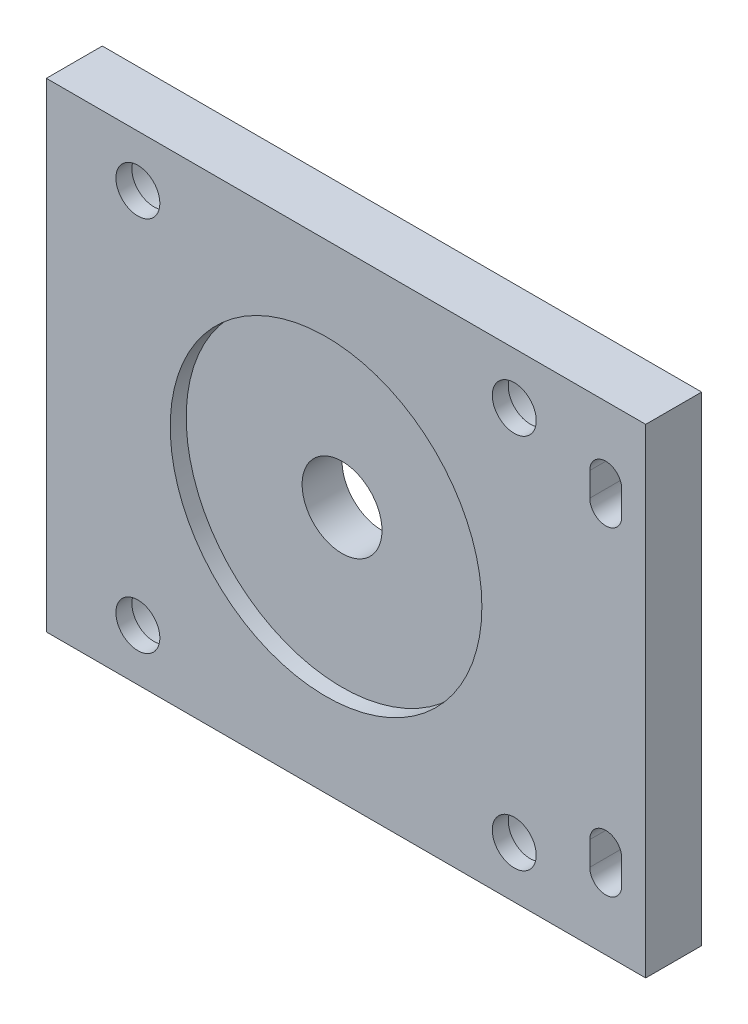
SolidWorks part; units mm, degrees
ref_plane "Front Plane" through (0, 0, 0) normal (0, 0, 1) x (1, 0, 0)
ref_plane "Top Plane" through (0, 0, 0) normal (0, 1, 0) x (1, 0, 0)
ref_plane "Right Plane" through (0, 0, 0) normal (1, 0, 0) x (0, 0, -1)
sketch "Sketch1" plane through (0, 0, 0) normal (0, 0, 1) x (1, 0, 0)
  line L1 (37.5, -30) -> (-37.5, -30)
  line L2 (37.5, -30) -> (37.5, 30)
  line L3 (37.5, 30) -> (-37.5, 30)
  line L4 (-37.5, -30) -> (-37.5, 30)
  line L5 (37.5, -30) -> (-37.5, 30) construction
  line L6 (37.5, 30) -> (-37.5, -30) construction
  point P0 (0, 0)
  dimension "D1" = 60
  dimension "D2" = 75
extrude "Boss-Extrude1" add sketch "Sketch1" along normal blind 7
sketch "Sketch2" plane through (0, 0, 0) normal (0, 0, -1) x (-1, 0, 0)
  line L0 (-37.5, 0) -> (37.5, 0) construction
  line L1 (-37.5, -30) -> (-37.5, 30) construction
  line L2 (37.5, 30) -> (37.5, -30) construction
  circle A0 centre (2.5, 0) radius 33.3047 construction
  point P7 (2.5, 0)
  point P19 (-21.05, -23.55)
  point P20 (26.05, -23.55)
  point P21 (26.05, 23.55)
  point P22 (-21.05, 23.55)
  dimension "D1" = 47.1
  dimension "D2" = 35
  dimension "D3" = 47.1
hole_wizard "CBORE for M5 SHCS1" positions "3DSketch1" profile "Sketch3" counterbore size "M5" standard "ANSI Metric" end condition through all
sketch3d "3DSketch1"
  point P17 (21.05, 23.55, 0)
  point P20 (-26.05, 23.55, 0)
  point P23 (-26.05, -23.55, 0)
  point P30 (21.05, -23.55, 0)
sketch "Sketch3" plane through (21.05, 23.55, 0) normal (1, 0, 0) x (0, 1, 0)
  line L0 (0, 0) -> (0, 7)
  line L1 (0, 7) -> (2.75, 7)
  line L3 (2.75, 7) -> (2.75, 5)
  line L4 (2.75, 5) -> (5, 5)
  line L5 (5, 5) -> (5, 0)
  line L7 (5, 0) -> (0, 0)
  line L11 (0, -6.35) -> (0, 107.95) construction
  dimension "Thru Hole Dia." = 5.5
  dimension "Thru Hole Depth" = 7
  dimension "C'Bore Dia." = 10
  dimension "C'Bore Depth" = 5
hole_wizard "Ø10.0 (10) Diameter Hole1" positions "3DSketch2" profile "Sketch4" hole size "Ø10.0" standard "ISO" end condition through all
sketch3d "3DSketch2"
  point P0 (-2.5, 0, 0)
sketch "Sketch4" plane through (-2.5, 0, 0) normal (1, 0, 0) x (0, 1, 0)
  line L0 (0, 0) -> (0, 7)
  line L1 (0, 7) -> (5, 7)
  line L2 (5, 7) -> (5, 0)
  line L5 (5, 0) -> (0, 0)
  line L11 (0, -6.35) -> (0, 107.95) construction
  dimension "Thru Hole Dia." = 10
  dimension "Thru Hole Depth" = 7
sketch "Sketch5" plane through (0, 0, 7) normal (0, 0, 1) x (1, 0, 0)
  circle A0 centre (-2.5, 0) radius 19.5
  dimension "D1" = 39
extrude "Cut-Extrude1" cut sketch "Sketch5" against normal blind 2
sketch "Sketch6" plane through (0, 0, 0) normal (0, 0, -1) x (-1, 0, 0)
  line L0 (-32.5, 30) -> (-32.5, -30) construction
  line L1 (-37.5, 30) -> (37.5, 30) construction
  line L2 (37.5, -30) -> (-37.5, -30) construction
  line L3 (-37.5, -30) -> (-37.5, 30) construction
  line L4 (-32.5, 18.5) -> (-32.5, 21.5) construction
  line L5 (-34.5, 18.5) -> (-34.5, 21.5)
  line L6 (-30.5, 18.5) -> (-30.5, 21.5)
  line L7 (-37.5, 0) -> (37.5, 0) construction
  line L8 (37.5, 30) -> (37.5, -30) construction
  line L9 (-32.5, -18.5) -> (-32.5, -21.5) construction
  line L10 (-34.5, -18.5) -> (-34.5, -21.5)
  line L11 (-30.5, -18.5) -> (-30.5, -21.5)
  arc A0 (-34.5, 18.5) -> (-30.5, 18.5) centre (-32.5, 18.5) ccw
  arc A1 (-30.5, 21.5) -> (-34.5, 21.5) centre (-32.5, 21.5) ccw
  arc A2 (-34.5, -18.5) -> (-30.5, -18.5) centre (-32.5, -18.5) cw
  arc A3 (-30.5, -21.5) -> (-34.5, -21.5) centre (-32.5, -21.5) cw
  point P10 (-32.5, 20)
  point P24 (-32.5, -20)
  dimension "D1" = 5
  dimension "D2" = 4
  dimension "D3" = 3
  dimension "D4" = 10
extrude "Cut-Extrude2" cut sketch "Sketch6" against normal through all
